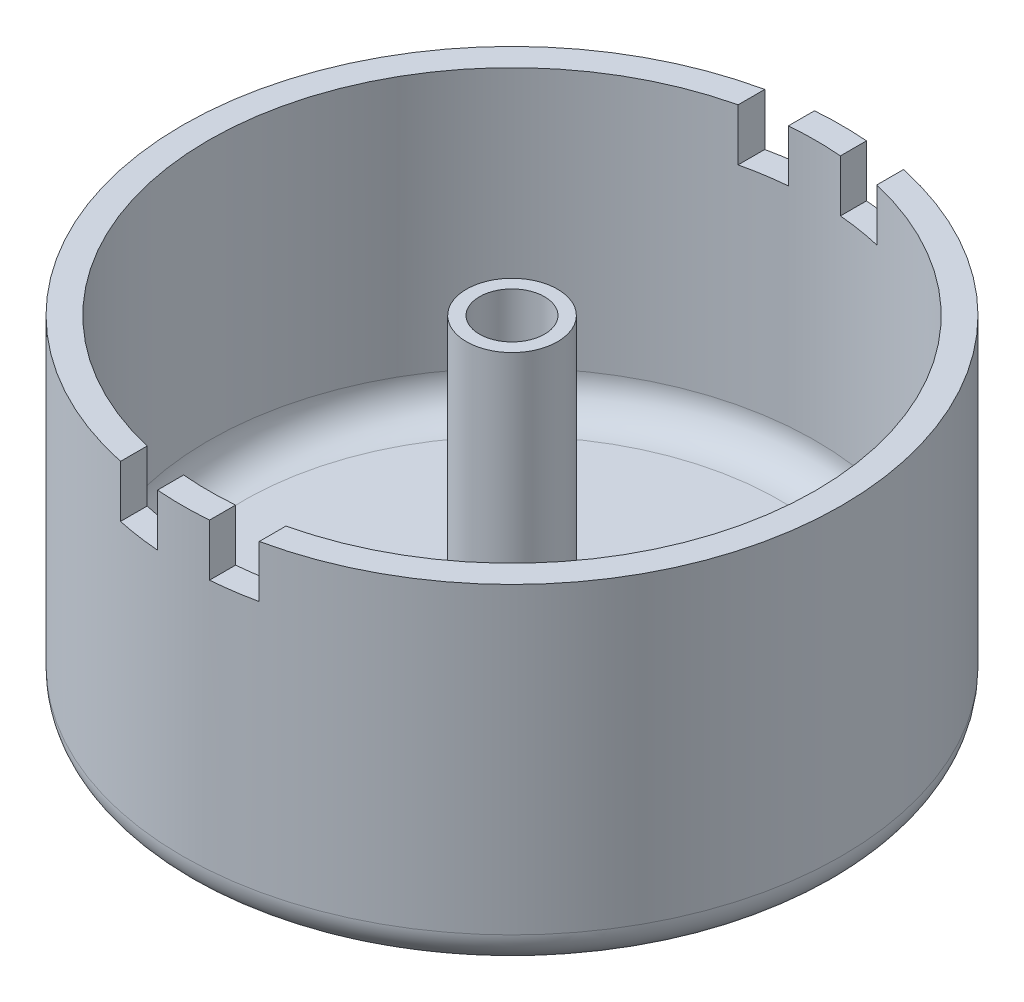
SolidWorks part; units mm, degrees
ref_plane "Front Plane" through (0, 0, 0) normal (0, 0, 1) x (1, 0, 0)
ref_plane "Top Plane" through (0, 0, 0) normal (0, 1, 0) x (1, 0, 0)
ref_plane "Right Plane" through (0, 0, 0) normal (1, 0, 0) x (0, 0, -1)
sketch "Sketch1" plane through (0, 0, 0) normal (0, 1, 0) x (1, 0, 0)
  line L1 (-17.5, 17.5) -> (17.5, 17.5) construction
  line L2 (-17.5, 17.5) -> (-17.5, -17.5) construction
  line L3 (-17.5, -17.5) -> (17.5, -17.5) construction
  line L4 (17.5, 17.5) -> (17.5, -17.5) construction
  line L5 (-17.5, 17.5) -> (17.5, -17.5) construction
  line L6 (-17.5, -17.5) -> (17.5, 17.5) construction
  circle A0 centre (0, 0) radius 17.5
  circle A1 centre (0, 0) radius 2.625
  circle A2 centre (0, 0) radius 19
  circle A3 centre (0, 0) radius 1.875
  circle A4 centre (0, 0) radius 1.5
  point P0 (0, 0)
  dimension "D3" = 5.25
  dimension "D4" = 38
  dimension "D5" = 0.75
  dimension "D6" = 3
  dimension "D1" = 35
  dimension "D2" = 35
extrude "Boss-Extrude1" add sketch "Sketch1" along normal blind 2.5 contours A2
extrude "Boss-Extrude2" add sketch "Sketch1<3>" along normal blind 17 from surface contours A2 A0 region at (-18.4626, 0, 0) starting at face at (0, 2.5, 19)
sketch "Sketch1<3>" plane through (0, 0, 0) normal (0, 1, 0) x (1, 0, 0) same geometry as "Sketch1"
extrude "Boss-Extrude3" add sketch "Sketch1<5>" along normal up to surface (19.5 mm away) from surface contours A1 A3 region at (-2.5508, 0, 0) up to face at (0, 19.5, 19) starting at face at (0, 2.5, 17.5)
sketch "Sketch1<5>" plane through (0, 0, 0) normal (0, 1, 0) x (1, 0, 0) same geometry as "Sketch1"
extrude "Cut-Extrude3" cut sketch "Sketch1<6>" along normal through all contours A3
sketch "Sketch1<6>" plane through (0, 0, 0) normal (0, 1, 0) x (1, 0, 0) same geometry as "Sketch1"
fillet "Fillet1" radius 2 1 edges at (0, 0, 19)
fillet "Fillet2" radius 2 2 edges at (0, 2.5, 2.625) (0, 2.5, 17.5)
sketch "Sketch2" plane through (0, 0, 0) normal (0, -1, 0) x (1, 0, 0)
  circle A0 centre (0, 0) radius 3.25
  dimension "D1" = 6.5
extrude "Cut-Extrude5" cut sketch "Sketch2" against normal blind 2.5
sketch "Sketch3" plane through (0, 19.5, 0) normal (0, 1, 0) x (1, 0, 0)
  line L0 (-4, 17.0367) -> (-4, 22.5)
  line L1 (-4, 22.5) -> (-1.5, 22.5)
  line L2 (4, 22.5) -> (4, 17.0367)
  line L3 (0, 0) -> (0, 13.2011) construction
  line L4 (0, 22.5) -> (0, 17.5) construction
  line L5 (-1.5, 22.5) -> (-1.5, 17.4356)
  line L6 (1.5, 17.4356) -> (1.5, 22.5)
  line L7 (0, 22.5) -> (1.5, 22.5) construction
  line L8 (1.5, 22.5) -> (4, 22.5)
  line L9 (-1.5, 22.5) -> (0, 22.5) construction
  circle A0 centre (0, 0) radius 17.5 construction
  circle A1 centre (0, 0) radius 17.5 construction
  arc A2 (-4, 17.0367) -> (-1.5, 17.4356) centre (0, 0) cw
  arc A3 (-1.5, 17.4356) -> (0, 17.5) centre (0, 0) cw construction
  arc A4 (1.5, 17.4356) -> (4, 17.0367) centre (0, 0) cw
  arc A5 (0, 17.5) -> (1.5, 17.4356) centre (0, 0) cw construction
  dimension "D3" = 2.5
  dimension "D1" = 8
  dimension "D2" = 22.5
extrude "Cut-Extrude6" cut sketch "Sketch3" against normal blind 3
mirror "Mirror1" about plane through (0, 0, 0) normal (0, 0, 1) of "Cut-Extrude6"
